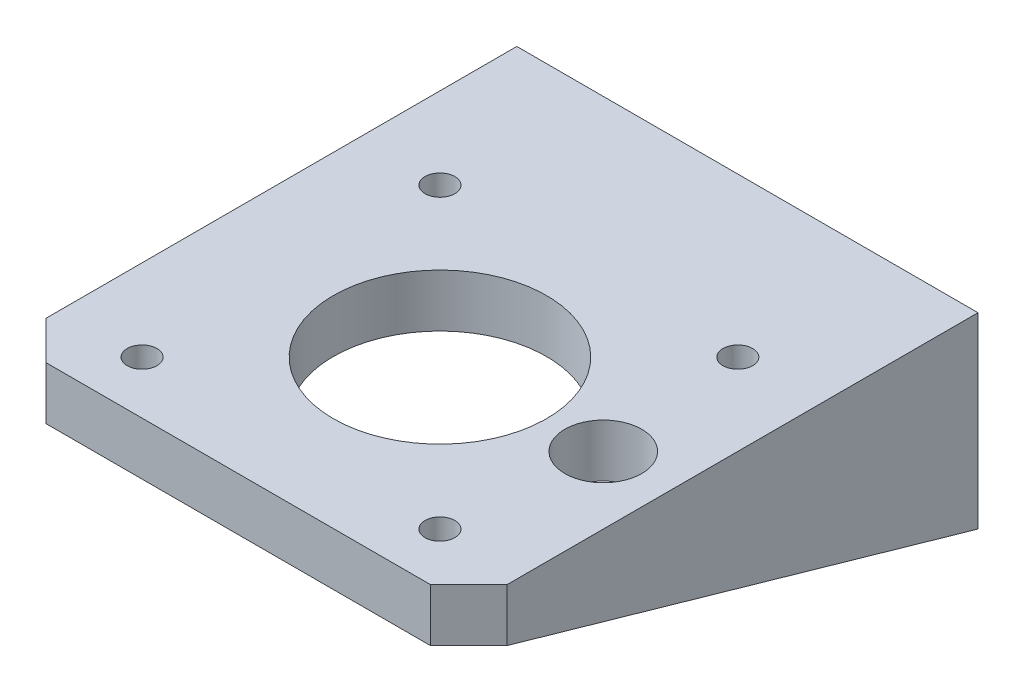
SolidWorks part; units mm, degrees
ref_plane "Alzado" through (0, 0, 0) normal (0, 0, 1) x (1, 0, 0)
ref_plane "Planta" through (0, 0, 0) normal (0, 1, 0) x (1, 0, 0)
ref_plane "Vista lateral" through (0, 0, 0) normal (1, 0, 0) x (0, 0, -1)
sketch "Croquis1" plane through (0, 0, 0) normal (0, 1, 0) x (1, 0, 0)
  line L0 (0, 4) -> (0, 49)
  line L1 (4, 53) -> (44, 53)
  line L2 (48, 49) -> (48, 4)
  line L3 (44, 0) -> (4, 0)
  line L4 (0, 49) -> (4, 53)
  line L5 (44, 53) -> (48, 49)
  line L6 (48, 4) -> (44, 0)
  line L7 (4, 0) -> (0, 4)
  circle A0 centre (8.5, 36.5) radius 1.55
  circle A1 centre (39.5, 36.5) radius 1.55
  circle A2 centre (8.5, 5.5) radius 1.55
  circle A3 centre (39.5, 5.5) radius 1.55
  circle A4 centre (24, 21) radius 11.1
  circle A5 centre (41, 21) radius 4
  point P0 (0, 0)
  point P1 (0, 53)
  point P4 (48, 53)
  point P5 (48, 0)
  dimension "D4" = 3.1
  dimension "D7" = 3.1
  dimension "D14" = 3.1
  dimension "D18" = 3.1
  dimension "D19" = 22.2
  dimension "D22" = 8
  dimension "D1" = 53
  dimension "D2" = 48
  dimension "D3" = 31
  dimension "D5" = 8.5
  dimension "D6" = 16.5
  dimension "D8" = 0
  dimension "D13" = 0
  dimension "D15" = 31
  dimension "D16" = 0
  dimension "D17" = 31
  dimension "D20" = 21
  dimension "D21" = 24
  dimension "D23" = 0
  dimension "D24" = 17
extrude "Saliente-Extruir1" add sketch "Croquis1" along normal blind 5.5
sketch "Croquis3" plane through (0, 5.5, 0) normal (0, 1, 0) x (1, 0, 0)
  line L0 (4, 53) -> (0, 53)
  line L1 (0, 53) -> (0, 49)
  line L10 (4, 53) -> (0, 49)
  line L11 (0, 49) -> (0, 4)
  line L12 (0, 4) -> (4, 0)
  line L13 (4, 0) -> (44, 0)
  line L14 (44, 0) -> (48, 4)
  line L15 (48, 4) -> (48, 49)
  line L16 (48, 49) -> (44, 53)
  line L17 (44, 53) -> (4, 53)
  line L18 (4, 53) -> (0, 49)
  dimension "D1" = 0
extrude "Saliente-Extruir2" add sketch "Croquis3" against normal blind 5.5
sketch "Croquis4" plane through (0, 0, 0) normal (-1, 0, 0) x (0, 0, 1)
  line L2 (-53, 0) -> (-53, 5.5) construction
  line L3 (-53, 0) -> (-53, 5.5)
  line L4 (-53, 0) -> (-53, -14)
  line L5 (-53, -14) -> (-4, 0)
  line L6 (-53, 5.5) -> (-4, 5.5)
  line L7 (-4, 5.5) -> (-4, 0) construction
  line L8 (-4, 5.5) -> (-4, 0)
  dimension "D1" = 14
extrude "Saliente-Extruir3" add sketch "Croquis4" against normal blind 3
sketch "Croquis5" plane through (0, 5.5, 0) normal (0, 1, 0) x (1, 0, 0)
  line L0 (48, 49) -> (48, 53)
  line L1 (48, 53) -> (44, 53)
  line L9 (0, 53) -> (0, 4)
  line L10 (0, 4) -> (4, 0)
  line L11 (4, 0) -> (44, 0)
  line L12 (44, 0) -> (48, 4)
  line L13 (48, 4) -> (48, 49)
  line L14 (48, 49) -> (44, 53)
  line L15 (44, 53) -> (0, 53)
  line L21 (48, 49) -> (44, 53)
  dimension "D1" = 0
extrude "Saliente-Extruir4" add sketch "Croquis5" against normal blind 5.5
sketch "Croquis6" plane through (48, 0, 0) normal (1, 0, 0) x (0, 0, -1)
  line L0 (4, 5.5) -> (4, 0) construction
  line L1 (53, 0) -> (53, 5.5) construction
  line L2 (4, 5.5) -> (53, 5.5) construction
  line L3 (53, 0) -> (53, -14) construction
  line L4 (53, -14) -> (4, 0) construction
  line L5 (4, 5.5) -> (4, 0)
  line L6 (53, 0) -> (53, 5.5)
  line L7 (4, 5.5) -> (53, 5.5)
  line L8 (53, 0) -> (53, -14)
  line L9 (53, -14) -> (4, 0)
extrude "Saliente-Extruir5" add sketch "Croquis6" against normal blind 3
sketch "Croquis7" plane through (0, 0, 0) normal (0, -1, 0) x (1, 0, 0)
  line L0 (45, -53) -> (3, -53)
  line L1 (3, -53) -> (3, -44)
  line L2 (3, -4) -> (3, -53) construction
  line L3 (3, -44) -> (45, -44)
  line L4 (45, -53) -> (45, -21) construction
  line L5 (45, -44) -> (45, -53)
  dimension "D1" = 9
extrude "Saliente-Extruir6" add sketch "Croquis7" along normal blind 14
sketch "Croquis9" plane through (0, 0, -44) normal (0, 0, 1) x (1, 0, 0)
  line L0 (3, -11.4286) -> (3, 0) construction
  line L1 (3, -11.4286) -> (3, 0)
  circle A0 centre (9, -5.7143) radius 1.55
  circle A1 centre (39, -5.7143) radius 1.55
  point P7 (3, -5.7143)
  dimension "D1" = 3.1
  dimension "D2" = 3.1
  dimension "D3" = 0
  dimension "D4" = 30
  dimension "D5" = 0
  dimension "D6" = 6
extrude "Cortar-Extruir1" cut sketch "Croquis9" against normal up to surface (9 mm away) contours A0 | A1 region at (9, -5.7143, -44) region at (39, -5.7143, -44) up to face at (24, -7.5, -53)
sketch "Croquis10" plane through (0, 0, -44) normal (0, 0, 1) x (1, 0, 0)
  circle A0 centre (39, -5.7143) radius 1.55 construction
  circle A1 centre (9, -5.7143) radius 1.55 construction
  circle A2 centre (39, -5.7143) radius 1.55
  circle A3 centre (9, -5.7143) radius 1.55
  circle A4 centre (9, -5.7143) radius 2.8
  circle A5 centre (39, -5.7143) radius 2.8
  circle M1 centre (39, -5.7143) radius 1.55
  circle M2 centre (9, -5.7143) radius 1.55
  dimension "D1" = 5.6
  dimension "D2" = 5.6
extrude "Cortar-Extruir2" cut sketch "Croquis10" against normal blind 3 contours A4 M2 | A5 M1 region at (6.2792, -5.7143, -44) region at (36.2792, -5.7143, -44)
sketch "Croquis11" plane through (3, 0, 0) normal (-1, 0, 0) x (0, 0, 1)
  line L3 (-44, -11.4286) -> (-53, -14)
  line L4 (-53, -14) -> (-44, -14)
  line L5 (-44, -14) -> (-44, -11.4286)
  line L6 (-44, -11.4286) -> (-53, -14)
  line L7 (-53, -14) -> (-44, -14)
  line L8 (-44, -14) -> (-44, -11.4286)
  dimension "D1" = 0
extrude "Cortar-Extruir3" cut sketch "Croquis11" against normal through all both and the other way through all
